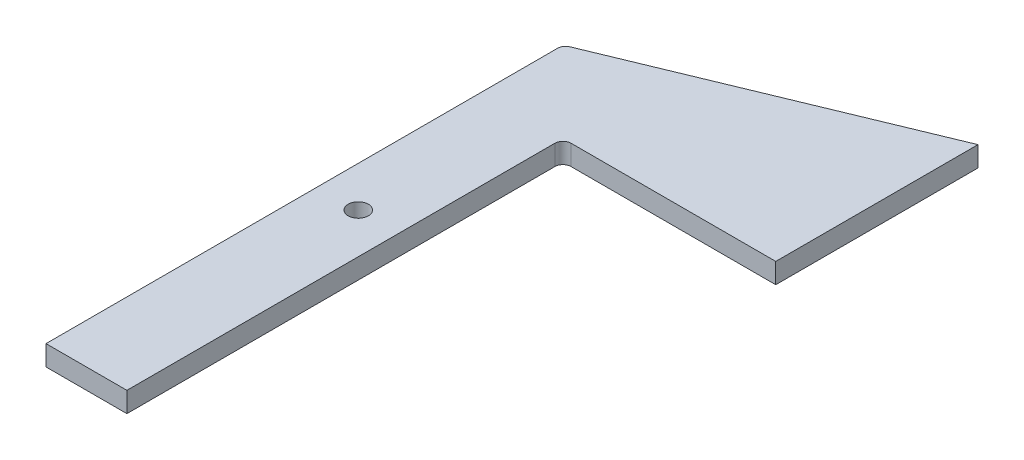
SolidWorks part; units mm, degrees
ref_plane "Front Plane" through (0, 0, 0) normal (0, 0, 1) x (1, 0, 0)
ref_plane "Top Plane" through (0, 0, 0) normal (0, 1, 0) x (1, 0, 0)
ref_plane "Right Plane" through (0, 0, 0) normal (1, 0, 0) x (0, 0, -1)
sketch "Sketch1" plane through (0, 0, 0) normal (0, 1, 0) x (1, 0, 0)
  line L0 (-50, 128.026) -> (42.202, 166.126)
  line L2 (-50, 128.026) -> (-50, -34.28)
  line L3 (-50, -34.28) -> (-24.6, -34.28)
  line L4 (-24.6, 102.626) -> (-24.6, -34.28)
  line L7 (-24.6, 102.626) -> (42.202, 102.626)
  line L8 (42.202, 128.026) -> (42.202, 102.626)
  line L10 (42.202, 128.026) -> (42.202, 166.126)
  dimension "D1" = 25.4
  dimension "D3" = 92.202
  dimension "D2" = 162.306
extrude "Boss-Extrude1" add sketch "Sketch1" along normal blind 6.35
sketch "Sketch2" plane through (0, 6.35, 0) normal (0, 1, 0) x (1, 0, 0)
  line L0 (-50, -34.28) -> (-24.6, -34.28) construction
  line L1 (-24.6, -34.28) -> (-24.6, 102.626) construction
  circle A0 centre (-37.3, 51.064) radius 3.175
  dimension "D1" = 6.35
  dimension "D2" = 85.344
  dimension "D3" = 12.7
extrude "Cut-Extrude1" cut sketch "Sketch2" against normal blind 6.35
fillet "Fillet1" radius 2.54 2 edges at (-24.6, 3.175, -102.626) (-50, 3.175, -128.026)
equation "\"t\"= 0.25in"
equation "\"D1@Sketch1\"=\"width\""
equation "\"width\"= 1in"
equation "\"D1@Boss-Extrude1\"=\"t\""
equation "\"D3@Sketch2\"=\"width\"/2"
equation "\"D1@Cut-Extrude1\"=\"t\""
